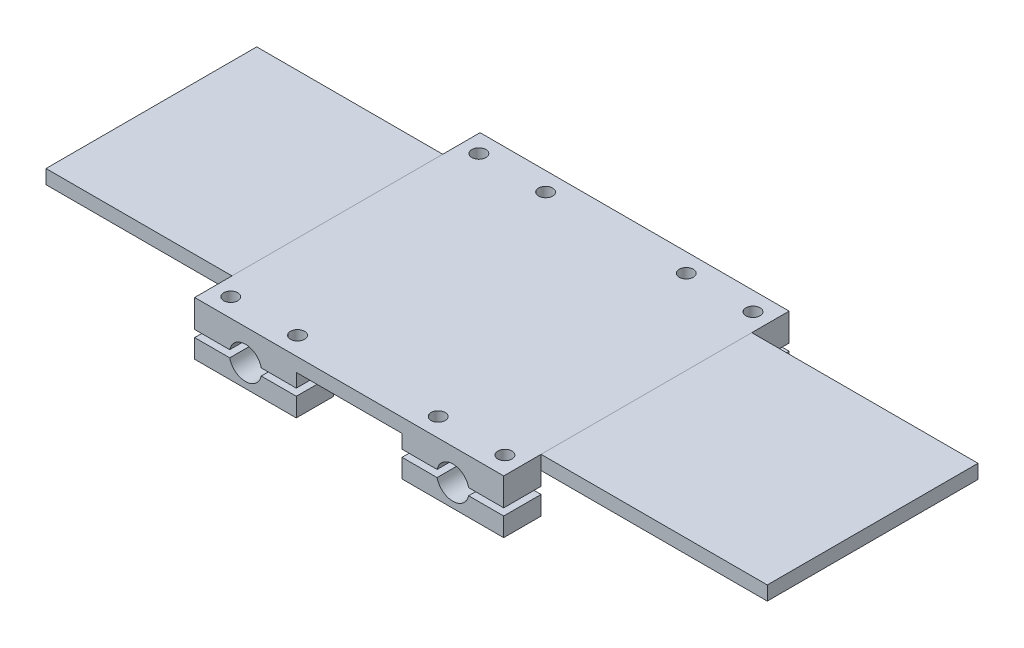
SolidWorks part; units mm, degrees
ref_plane "Front Plane" through (0, 0, 0) normal (0, 0, 1) x (1, 0, 0)
ref_plane "Top Plane" through (0, 0, 0) normal (0, 1, 0) x (1, 0, 0)
ref_plane "Right Plane" through (0, 0, 0) normal (1, 0, 0) x (0, 0, -1)
sketch "Sketch1" plane through (0, 0, 0) normal (0, 0, 1) x (1, 0, 0)
  line L0 (73.8188, 0) -> (0, 0) construction
  line L1 (-110, -15.875) -> (110, -15.875)
  line L2 (-110, -15.875) -> (-110, 15.875)
  line L3 (-110, 15.875) -> (110, 15.875)
  line L4 (110, -15.875) -> (110, 15.875)
  line L5 (-110, -15.875) -> (110, 15.875) construction
  line L6 (-110, 15.875) -> (110, -15.875) construction
  line L7 (0, 0) -> (-73.8187, 0) construction
  circle A1 centre (-73.8187, 0) radius 11.5
  circle A2 centre (73.8188, 0) radius 11.5
  point P0 (0, 0)
  dimension "D1" = 147.6375
  dimension "D4" = 23
  dimension "D2" = 31.75
  dimension "D3" = 220
extrude "Boss-Extrude1" add sketch "Sketch1" along normal blind 203.2
sketch "Sketch3" plane through (0, 0, 203.2) normal (0, 0, 1) x (1, 0, 0)
  line L0 (110, -15.875) -> (110, 15.875) construction
  line L1 (-110, 15.875) -> (110, 15.875)
  line L2 (-110, 15.875) -> (-110, 22.225)
  line L3 (-110, 22.225) -> (110, 22.225)
  line L4 (110, 15.875) -> (110, 22.225)
  dimension "D1" = 6.35
extrude "Boss-Extrude2" add sketch "Sketch3" against normal up to surface (203.2 mm away) up to face at (-62.3188, 0, 0)
sketch "Sketch4" plane through (-110, 0, 0) normal (-1, 0, 0) x (0, 0, 1)
  line L0 (203.2, -15.875) -> (0, -15.875) construction
  line L1 (26.6, -15.875) -> (176.6, -15.875)
  line L2 (26.6, -15.875) -> (26.6, 12.225)
  line L3 (26.6, 12.225) -> (176.6, 12.225)
  line L4 (176.6, -15.875) -> (176.6, 12.225)
  line L5 (0, 0) -> (26.6, 0) construction
  line L6 (26.6, 0) -> (176.6, 0) construction
  line L7 (176.6, 0) -> (203.2, 0) construction
  line L8 (203.2, 22.225) -> (203.2, -15.875) construction
  line L9 (0, 22.225) -> (203.2, 22.225) construction
  dimension "D1" = 10
  dimension "D2" = 150
extrude "Cut-Extrude1" cut sketch "Sketch4" against normal blind 253.2
sketch "Sketch5" plane through (0, 0, 0) normal (0, 0, -1) x (-1, 0, 0)
  line L0 (110, -15.875) -> (-110, -15.875) construction
  line L1 (-37.6375, -15.875) -> (37.6375, -15.875)
  line L2 (-37.6375, -15.875) -> (-37.6375, 12.225)
  line L3 (-37.6375, 12.225) -> (37.6375, 12.225)
  line L4 (37.6375, -15.875) -> (37.6375, 12.225)
  line L5 (-110, 22.225) -> (110, 22.225) construction
  line L6 (0, 0) -> (-37.6375, 0) construction
  line L7 (0, 0) -> (37.6375, 0) construction
  line L8 (-37.6375, 0) -> (-73.8188, 0) construction
  line L9 (-73.8188, 0) -> (-110, 0) construction
  line L10 (-110, -15.875) -> (-110, 22.225) construction
  dimension "D1" = 10
extrude "Cut-Extrude2" cut sketch "Sketch5" against normal blind 203.2
sketch "Sketch6" plane through (0, -15.875, 0) normal (0, -1, 0) x (1, 0, 0)
  line L0 (-110, 189.9) -> (-97.5688, 189.9) construction
  line L2 (-97.5688, 189.9) -> (-50.0688, 189.9) construction
  line L3 (-50.0688, 189.9) -> (-37.6375, 189.9) construction
  line L5 (-110, 13.3) -> (-97.5688, 13.3) construction
  line L6 (-110, 26.6) -> (-110, 0) construction
  line L7 (-97.5688, 13.3) -> (-50.0688, 13.3) construction
  line L8 (-50.0688, 13.3) -> (-37.6375, 13.3) construction
  line L9 (-37.6375, 26.6) -> (-37.6375, 0) construction
  line L10 (37.6375, 203.2) -> (37.6375, 176.6) construction
  line L11 (37.6375, 26.6) -> (37.6375, 0) construction
  line L12 (37.6375, 13.3) -> (50.0688, 13.3) construction
  line L13 (50.0688, 13.3) -> (97.5687, 13.3) construction
  line L14 (97.5687, 13.3) -> (110, 13.3) construction
  line L16 (-62.3188, 203.2) -> (-85.3187, 203.2) construction
  line L18 (110, 189.9) -> (97.5687, 189.9) construction
  line L19 (97.5687, 189.9) -> (50.0688, 189.9) construction
  line L20 (50.0688, 189.9) -> (37.6375, 189.9) construction
  line L22 (-62.3188, 203.2) -> (-85.3187, 203.2)
  line L23 (-85.3187, 203.2) -> (-85.3187, 0) construction
  line L24 (-110, 0) -> (-37.6375, 0) construction
  line L25 (-62.3188, 203.2) -> (-62.3188, 0) construction
  line L28 (-37.6375, 203.2) -> (-37.6375, 176.6) construction
  line L29 (-110, 203.2) -> (-110, 176.6) construction
  line L30 (110, 203.2) -> (110, 176.6) construction
  circle A0 centre (-50.0688, 189.9) radius 5
  circle A1 centre (-97.5688, 189.9) radius 5
  circle A2 centre (-97.5688, 13.3) radius 5
  circle A3 centre (-50.0688, 13.3) radius 5
  circle A4 centre (50.0688, 13.3) radius 5
  circle A5 centre (97.5687, 13.3) radius 5
  circle A6 centre (97.5687, 189.9) radius 5
  circle A7 centre (50.0688, 189.9) radius 5
  dimension "D1" = 10
  dimension "D2" = 47.5
extrude "Cut-Extrude3" cut sketch "Sketch6" against normal blind 203.2 contours A4 | A5 | A3 | A2 | A1 | A0 | A7 | A6
sketch "Sketch7" plane through (0, 0, 0) normal (0, 0, -1) x (-1, 0, 0)
  line L0 (-110, -15.875) -> (-110, 22.225) construction
  line L1 (110, -2.5) -> (-110, -2.5)
  line L2 (110, -2.5) -> (110, 2.5)
  line L3 (110, 2.5) -> (-110, 2.5)
  line L4 (-110, -2.5) -> (-110, 2.5)
  line L5 (110, -2.5) -> (-110, 2.5) construction
  line L6 (110, 2.5) -> (-110, -2.5) construction
  point P0 (0, 0)
  dimension "D1" = 5
extrude "Cut-Extrude4" cut sketch "Sketch7" against normal blind 203.2
sketch "Sketch8" plane through (-110, 0, 0) normal (-1, 0, 0) x (0, 0, 1)
  line L0 (176.6, 12.225) -> (26.6, 12.225) construction
  line L1 (176.6, 12.225) -> (26.6, 12.225)
  line L2 (176.6, 12.225) -> (176.6, 22.225)
  line L3 (176.6, 22.225) -> (26.6, 22.225)
  line L4 (26.6, 12.225) -> (26.6, 22.225)
  line L5 (0, 22.225) -> (203.2, 22.225) construction
  line M4 (26.6, 12.225) -> (176.6, 12.225)
  line M8 (203.2, 22.225) -> (0, 22.225)
extrude "Boss-Extrude3" add sketch "Sketch8" along normal blind 132.4137 contours L4 L2 M4 M8 region at (-110, 17.225, 101.6)
sketch "Sketch9" plane through (110, 0, 0) normal (1, 0, 0) x (0, 0, -1)
  line L0 (-176.6, 12.225) -> (-26.6, 12.225) construction
  line L1 (-176.6, 12.225) -> (-26.6, 12.225)
  line L2 (-176.6, 12.225) -> (-176.6, 22.225)
  line L3 (-176.6, 22.225) -> (-26.6, 22.225)
  line L4 (-26.6, 12.225) -> (-26.6, 22.225)
  line L5 (0, 22.225) -> (-203.2, 22.225) construction
extrude "Boss-Extrude4" add sketch "Sketch9" along normal blind 161.0473
ref_plane "Plane1" through (-110, 0, 0) normal (-1, 0, 0) x (0, 0, 1)
ref_plane "Plane2" through (110, 0, 0) normal (1, 0, 0) x (0, 0, -1)
split line "Split Line1"
split line "Split Line2"
